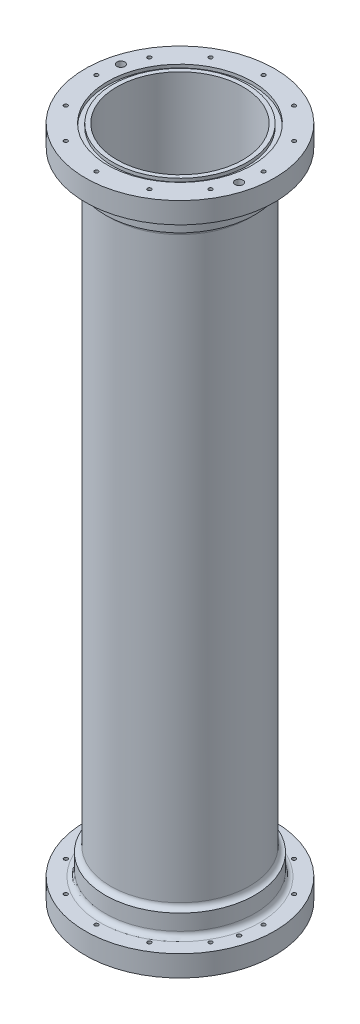
SolidWorks part; units mm, degrees
material "6061-T6 (SS)"
ref_plane "Front Plane" through (0, 0, 0) normal (0, 0, 1) x (1, 0, 0)
ref_plane "Top Plane" through (0, 0, 0) normal (0, 1, 0) x (1, 0, 0)
ref_plane "Right Plane" through (0, 0, 0) normal (1, 0, 0) x (0, 0, -1)
sketch "Sketch2" plane through (0, 0, 0) normal (0, 1, 0) x (1, 0, 0)
  circle A0 centre (0, 0) radius 38.1
  circle A1 centre (0, 0) radius 41.91
  dimension "D1" = 83.82
  dimension "D2" = 76.2
extrude "Base Cylinder" add sketch "Sketch2" along normal blind 406.4
sketch "Sketch3" plane through (0, 0, 0) normal (0, -1, 0) x (1, 0, 0)
  circle A0 centre (0, 0) radius 38.1
  circle A1 centre (0, 0) radius 57.15
  dimension "D1" = 114.3
extrude "Aft Flange" add sketch "Sketch3" against normal blind 12.7
sketch "Sketch6" plane through (0, 0, 0) normal (0, -1, 0) x (1, 0, 0)
  circle A0 centre (0, 0) radius 43.7261
  circle A1 centre (0, 0) radius 40.6527
  dimension "D1" = 87.4522
  dimension "D2" = 81.3054
extrude "Aft O-Ring" cut sketch "Sketch6" against normal blind 1.9812
sketch "Sketch33" plane through (0, 12.7, 0) normal (0, 1, 0) x (1, 0, 0)
  circle A0 centre (0, 0) radius 41.91
  circle A1 centre (0, 0) radius 45.085
  dimension "D1" = 83.82
  dimension "D2" = 90.17
extrude "Boss-Extrude1" add sketch "Sketch33" along normal blind 12.7
sketch "Sketch For Bolt Holes" plane through (0, 0, 0) normal (0, -1, 0) x (1, 0, 0)
  circle A0 centre (-50.438, 0) radius 1.5875
  circle A1 centre (-43.6806, 25.219) radius 1.5875
  circle A2 centre (-25.219, 43.6806) radius 1.5875
  circle A3 centre (0, 50.438) radius 1.5875
  circle A4 centre (25.219, 43.6806) radius 1.5875
  circle A5 centre (43.6806, 25.219) radius 1.5875
  circle A6 centre (50.438, 0) radius 1.5875
  circle A7 centre (43.6806, -25.219) radius 1.5875
  circle A8 centre (25.219, -43.6806) radius 1.5875
  circle A9 centre (0, -50.438) radius 1.5875
  circle A10 centre (-25.219, -43.6806) radius 1.5875
  circle A11 centre (-43.6806, -25.219) radius 1.5875
  point P25 (0, 0)
  point P36 (0, 0)
  dimension "D2" = 3.175
  dimension "D1" = 50.438
  dimension "D3" = 12
hole_wizard "Tap Drill for #4-40 Tap1" positions "Sketch8" profile "Sketch9" hole size "#4-40" standard "ANSI Inch"
sketch "Sketch8" plane through (0, 0, 0) normal (0, -1, 0) x (-1, 0, 0)
  point P0 (-25.219, -43.6806)
  point P3 (-43.6806, -25.219)
  point P6 (-50.438, 0)
  point P9 (-43.6806, 25.219)
  point P12 (-25.219, 43.6806)
  point P15 (0, 50.438)
  point P18 (25.219, 43.6806)
  point P21 (43.6806, 25.219)
  point P24 (50.438, 0)
  point P27 (43.6806, -25.219)
  point P30 (25.219, -43.6806)
  point P33 (0, -50.438)
  point P36 (-25.219, -43.6806)
  point P38 (-43.6806, -25.219)
  point P40 (-50.438, 0)
sketch "Sketch9" plane through (25.219, 0, 43.6806) normal (1, 0, 0) x (0, 0, -1)
  line L0 (0, 0) -> (0, 26.0792)
  line L1 (0, 26.0792) -> (1.1303, 25.4)
  line L2 (1.1303, 25.4) -> (1.1303, 0)
  line L5 (1.1303, 0) -> (0, 0)
  line L10 (0, 26.0792) -> (-1.1303, 25.4) construction
  line L11 (0, -6.35) -> (0, 107.95) construction
  dimension "Hole Dia." = 2.2606
  dimension "Hole Depth" = 25.4
  dimension "Drill Angle" = 118
sketch "Dowel Hole Sketch" plane through (0, 0, 0) normal (0, -1, 0) x (1, 0, 0)
  line L0 (0, 0) -> (-50.438, 0) construction
  line L1 (0, 0) -> (-48.7194, -13.0543) construction
  line L2 (0, 0) -> (0, -50.438) construction
  line L3 (0, 0) -> (48.7194, 13.0543) construction
  circle A0 centre (0, 0) radius 50.438
  circle A1 centre (-48.7194, -13.0543) radius 4.6172
  circle A2 centre (48.7194, 13.0543) radius 3.4532
  dimension "D1" = 15
hole_wizard "3/16 (0.1875) Press Dowel Hole1" positions "Sketch14" profile "Sketch12" hole size "3/16" standard "ANSI Inch"
sketch "Sketch14" plane through (0, 0, 0) normal (0, -1, 0) x (-1, 0, 0)
  point P0 (48.7194, 13.0543)
  point P3 (-48.7194, -13.0543)
sketch "Sketch12" plane through (-48.7194, 0, -13.0543) normal (1, 0, 0) x (0, 0, -1)
  line L0 (0, 0) -> (0, 7.7808)
  line L1 (0, 7.7808) -> (2.3812, 6.35)
  line L2 (2.3812, 6.35) -> (2.3812, 0)
  line L5 (2.3812, 0) -> (0, 0)
  line L10 (0, 7.7808) -> (-2.3813, 6.35) construction
  line L11 (0, -6.35) -> (0, 107.95) construction
  dimension "Hole Dia." = 4.7625
  dimension "Hole Depth" = 6.35
  dimension "Drill Angle" = 118
hole_wizard "3/32 (0.09375) Diameter Hole1" positions "Sketch19" profile "Sketch21" hole size "3/32" standard "ANSI Inch" end condition up to next
sketch "Sketch19" plane through (0, 0, 0) normal (0, -1, 0) x (-1, 0, 0)
  point P0 (-48.7194, -13.0543)
  point P3 (48.7194, 13.0543)
sketch "Sketch21" plane through (48.7194, 0, 13.0543) normal (1, 0, 0) x (0, 0, -1)
  line L0 (0, 0) -> (0, 398.6192)
  line L1 (0, 398.6192) -> (1.1906, 398.6192)
  line L2 (1.1906, 398.6192) -> (1.1906, 0)
  line L5 (1.1906, 0) -> (0, 0)
  line L11 (0, -6.35) -> (0, 107.95) construction
  dimension "Thru Hole Dia." = 2.3812
  dimension "Thru Hole Depth" = 398.6192
ref_plane "Hoop Mid-Plane" through (0, 203.2, 0) normal (0, 1, 0) x (1, 0, 0)
mirror "Forward Mirror BC and Pin" about plane through (0, 203.2, 0) normal (0, 1, 0) of "Aft Flange", "Tap Drill for #4-40 Tap1", "3/32 (0.09375) Diameter Hole1", "3/16 (0.1875) Press Dowel Hole1", "Aft O-Ring", "Boss-Extrude1"
fillet "Fillet2" radius 3.175 4 edges at (0, 381, 41.91) (0, 393.7, 45.085) (0, 12.7, -45.085) (0, 25.4, 41.91)
ref_plane "PressureTapHolePlane" [suppressed] through (0, 0, 47.625) normal (0, 0, 1) x (1, 0, 0)
ref_plane "PressureTapHole2Plane" [suppressed] through (0, 0, -47.625) normal (0, 0, 1) x (1, 0, 0)
